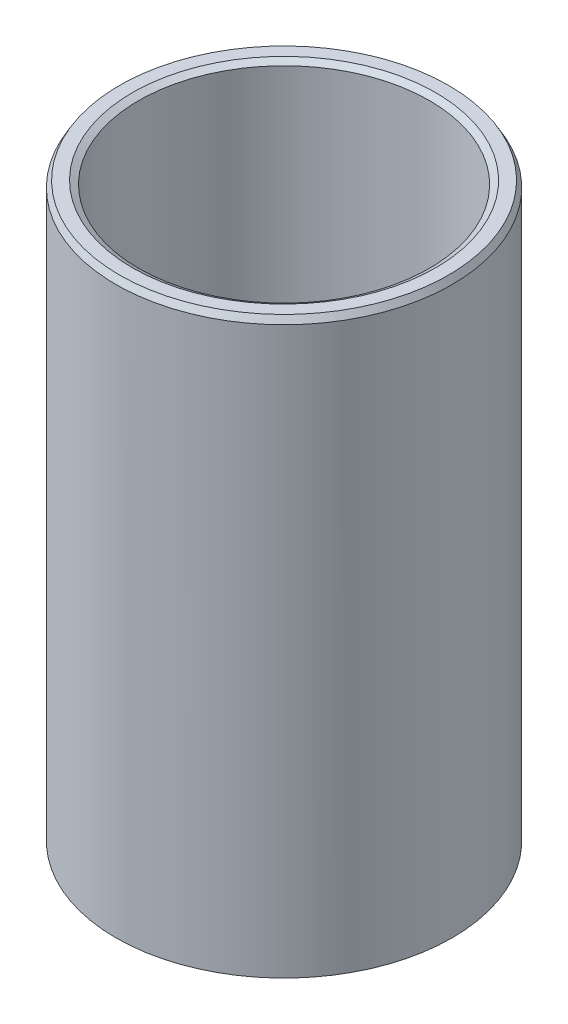
SolidWorks part; units mm, degrees
ref_plane "Front Plane" through (0, 0, 0) normal (0, 0, 1) x (1, 0, 0)
ref_plane "Top Plane" through (0, 0, 0) normal (0, 1, 0) x (1, 0, 0)
ref_plane "Right Plane" through (0, 0, 0) normal (1, 0, 0) x (0, 0, -1)
sketch "Sketch1" plane through (0, 0, 0) normal (0, 1, 0) x (1, 0, 0)
  circle A0 centre (0, 0) radius 45
  dimension "SLEEVE_OD" = 90
extrude "Boss-Extrude1" add sketch "Sketch1" along normal blind 154.1657
sketch "Sketch2" plane through (0, 0, 0) normal (0, 1, 0) x (1, 0, 0)
  circle A0 centre (0, 0) radius 38.9231
  dimension "BORE_D" = 77.8461
extrude "Cut-Extrude1" cut sketch "Sketch2" along normal through all
chamfer "Chamfer1" distance 1.6949 angle 30 4 edges at (0, 154.1657, 38.9231) (0, 0, 38.9231) (0, 0, 45) (0, 154.1657, 45) first distance on face at (0, 154.1657, 38.9231) first distance on face at (0, 0, 38.9231) first distance on face at (0, 154.1657, 45)
